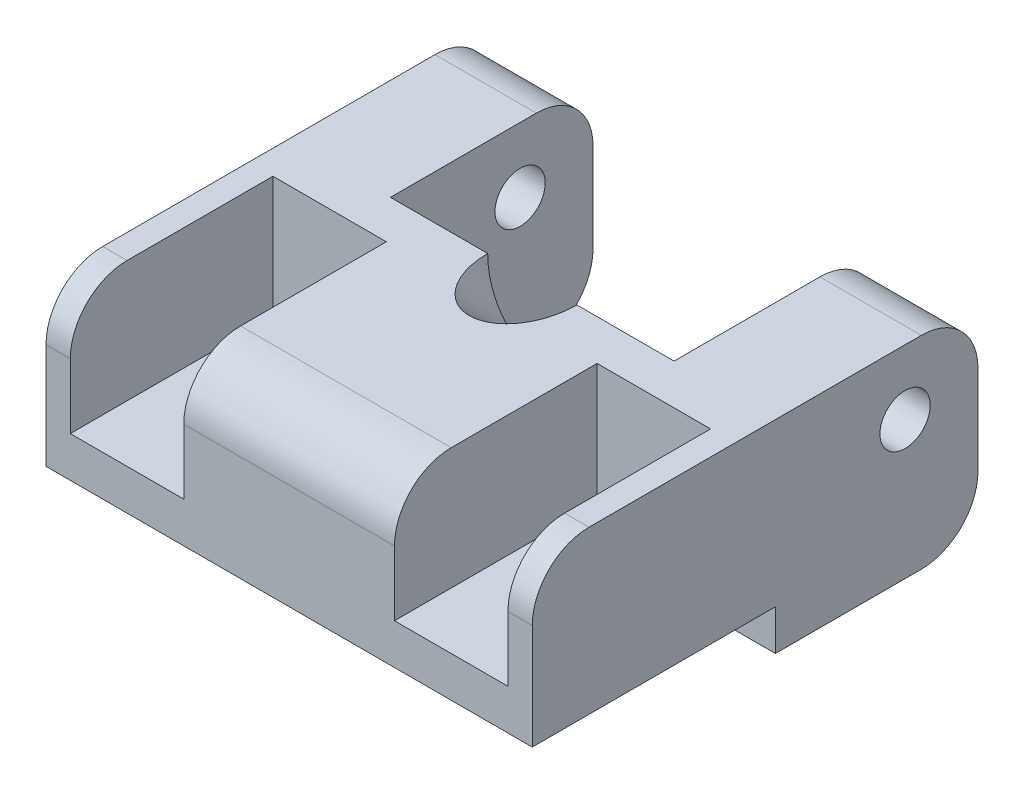
SolidWorks part; units mm, degrees
ref_plane "Alzado" through (0, 0, 0) normal (0, 0, 1) x (1, 0, 0)
ref_plane "Planta" through (0, 0, 0) normal (0, 1, 0) x (1, 0, 0)
ref_plane "Vista lateral" through (0, 0, 0) normal (1, 0, 0) x (0, 0, -1)
sketch "Croquis1" plane through (0, 0, 0) normal (0, 1, 0) x (1, 0, 0)
  line L0 (30, 0) -> (30, 30) construction
  line L1 (0, 0) -> (60, 0)
  line L2 (0, 0) -> (0, 30)
  line L3 (12.5, 30) -> (47.5, 30)
  line L4 (60, 0) -> (60, 30)
  line L5 (0, 15) -> (10, 15) construction
  line L6 (10, 15) -> (50, 15) construction
  line L7 (50, 15) -> (60, 15) construction
  line L8 (12.5, 55) -> (47.5, 55) construction
  line L10 (0, 30) -> (0, 55)
  line L11 (0, 55) -> (12.5, 55)
  line L12 (12.5, 30) -> (12.5, 55)
  line L14 (60, 30) -> (60, 55)
  line L15 (60, 55) -> (47.5, 55)
  line L16 (47.5, 30) -> (47.5, 55)
  line L17 (47.5, 30) -> (60, 30) construction
  circle A0 centre (10, 15) radius 2.5
  circle A1 centre (50, 15) radius 2.5
  point P9 (30, 15)
  dimension "D4" = 5
  dimension "D1" = 60
  dimension "D2" = 30
  dimension "D3" = 40
  dimension "D5" = 35
  dimension "D6" = 25
extrude "Saliente-Extruir1" add sketch "Croquis1" along normal blind 5
sketch "Croquis2" plane through (0, 5, 0) normal (0, 1, 0) x (1, 0, 0)
  line L0 (10, 15) -> (3, 15) construction
  line L2 (3, 0) -> (3, 25)
  line L3 (3, 25) -> (17, 25)
  line L4 (57, 0) -> (57, 25)
  line L5 (50, 15) -> (57, 15) construction
  line L6 (57, 0) -> (60, 0)
  line L7 (0, 0) -> (60, 0) construction
  line L8 (0, 55) -> (0, 0)
  line L9 (0, 0) -> (60, 0)
  line L10 (60, 0) -> (60, 55)
  line L11 (60, 55) -> (47.5, 55)
  line L12 (47.5, 55) -> (47.5, 30)
  line L13 (47.5, 30) -> (12.5, 30)
  line L14 (12.5, 30) -> (12.5, 55)
  line L15 (12.5, 55) -> (0, 55)
  line L16 (0, 55) -> (0, 0)
  line L17 (0, 0) -> (3, 0)
  line L18 (60, 0) -> (60, 55)
  line L19 (60, 55) -> (47.5, 55)
  line L20 (47.5, 55) -> (47.5, 30)
  line L21 (47.5, 30) -> (12.5, 30)
  line L22 (12.5, 30) -> (12.5, 55)
  line L23 (12.5, 55) -> (0, 55)
  line L24 (17, 10.0834) -> (43, 10.0834) construction
  line L26 (17, 25) -> (17, 0)
  line L27 (17, 0) -> (43, 0)
  line L28 (43, 25) -> (43, 0)
  line L29 (30, 24.621) -> (30, 10.0834) construction
  line L30 (43, 25) -> (57, 25)
  line L31 (17, 25) -> (43, 25) construction
  line L32 (30, 30) -> (30, 24.621) construction
  line L33 (10, 15) -> (17, 15) construction
  dimension "D2" = 7
  dimension "D3" = 25
  dimension "D1" = 0
extrude "Saliente-Extruir2" add sketch "Croquis2" along normal blind 15 and the other way blind 10
sketch "Croquis4" plane through (0, 0, 0) normal (-1, 0, 0) x (0, 0, 1)
  line L0 (-52.8418, 12) -> (-30, 12) construction
  line L1 (-55, 20) -> (-55, -5) construction
  line L2 (-30, 20) -> (-30, -5) construction
  line L3 (-55.2056, -8) -> (-17.2761, -8) construction
  line L4 (-49.0451, 20) -> (-49.0451, -5) construction
  line L5 (-30, -5) -> (0, -5)
  line L6 (-30, -5) -> (-30, 0)
  line L7 (-30, 0) -> (0, 0)
  line L8 (0, -5) -> (0, 0)
  line L9 (-55, 20) -> (0, 20) construction
  line L10 (-55, -5) -> (0, -5) construction
  circle A0 centre (-46, 12) radius 3.1
  dimension "D1" = 6.2
  dimension "D2" = 8
  dimension "D3" = 9
  dimension "D4" = 20
extrude "Cortar-Extruir2" cut sketch "Croquis4" against normal up to surface (60 mm away) up to face at (60, 7.5, -27.5)
fillet "Redondeo2" radius 7 7 edges at (1.5, 20, 0) (58.5, 20, 0) (6.25, -5, -55) (53.75, -5, -55) (53.75, 20, -55) (6.25, 20, -55) (30, 20, 0)
ref_plane "Plano1" through (0, -5, -5) normal (0, -0.7071, -0.7071) x (-1, 0, 0)
sketch "Croquis5" plane through (0, -5, -5) normal (0, -0.7071, -0.7071) x (-1, 0, 0)
  line L0 (-47.5, 35.3553) -> (-12.5, 35.3553) construction
  circle A0 centre (-30, 35.3553) radius 5.5
  dimension "D1" = 11
extrude "Cortar-Extruir3" cut sketch "Croquis5" against normal blind 10 and the other way blind 10
